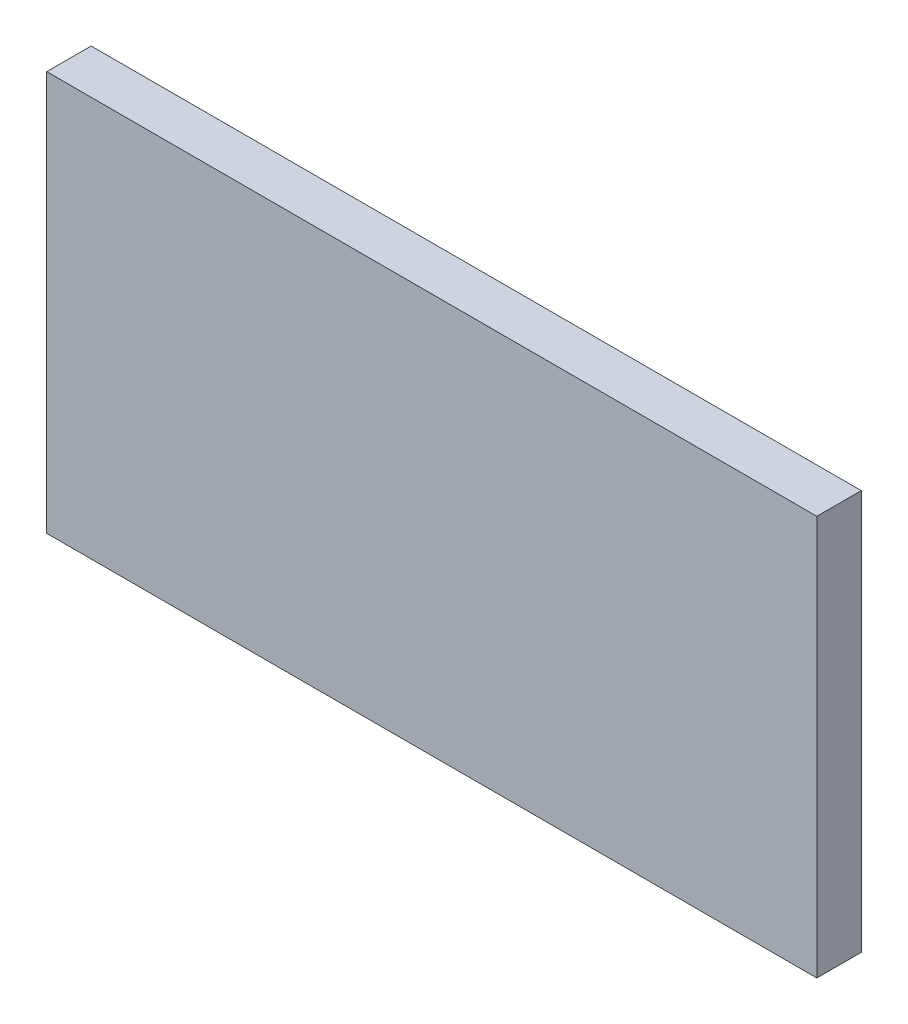
SolidWorks part; units mm, degrees
ref_plane "Front Plane" through (0, 0, 0) normal (0, 0, 1) x (1, 0, 0)
ref_plane "Top Plane" through (0, 0, 0) normal (0, 1, 0) x (1, 0, 0)
ref_plane "Right Plane" through (0, 0, 0) normal (1, 0, 0) x (0, 0, -1)
sketch "Sketch1" plane through (0, 0, 0) normal (0, 0, 1) x (1, 0, 0)
  line L5 (165.1, -85.725) -> (-165.1, -85.725)
  line L6 (165.1, -85.725) -> (165.1, 85.725)
  line L7 (165.1, 85.725) -> (-165.1, 85.725)
  line L8 (-165.1, -85.725) -> (-165.1, 85.725)
  line L9 (165.1, -85.725) -> (-165.1, 85.725) construction
  line L10 (165.1, 85.725) -> (-165.1, -85.725) construction
  point P0 (0, 0)
  dimension "D1" = 330.2
  dimension "D2" = 171.45
extrude "Boss-Extrude1" add sketch "Sketch1" along normal blind 19.05
